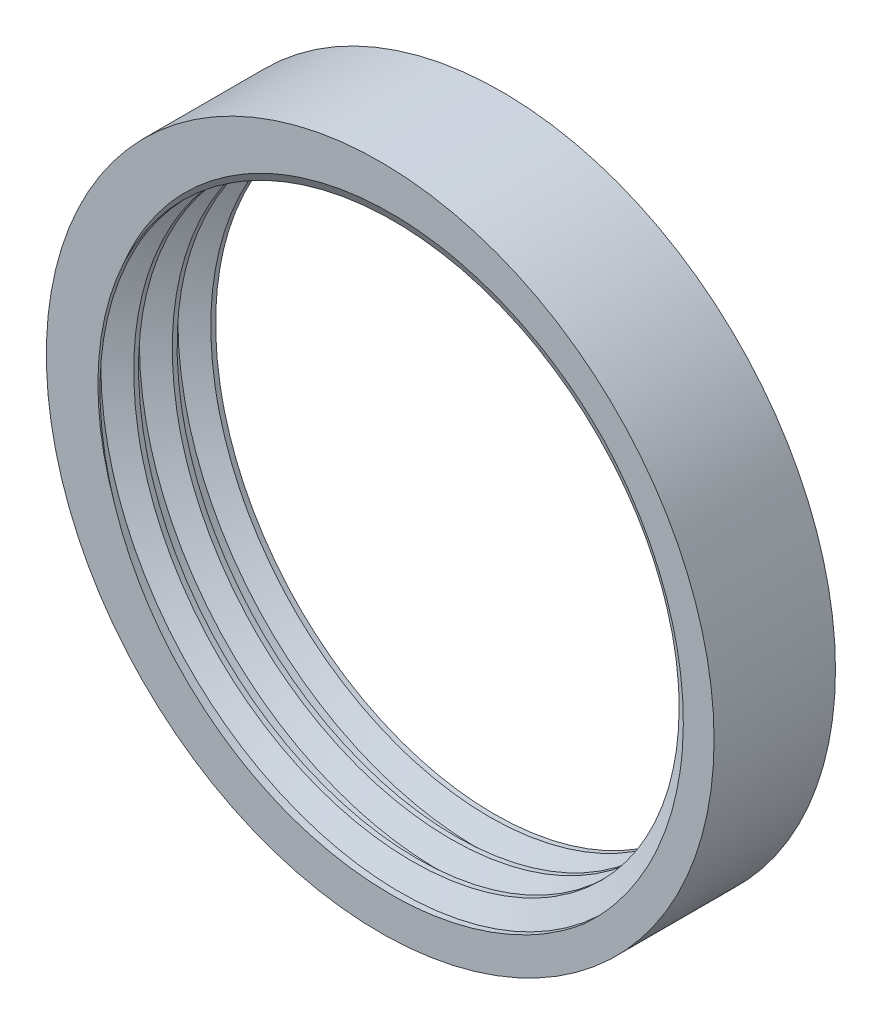
SolidWorks part; units mm, degrees
ref_plane "Plano frontal" through (0, 0, 0) normal (0, 0, 1) x (1, 0, 0)
ref_plane "Plano superior" through (0, 0, 0) normal (0, 1, 0) x (1, 0, 0)
ref_plane "Plano direito" through (0, 0, 0) normal (1, 0, 0) x (0, 0, -1)
sketch "Esboço1" plane through (0, 0, 0) normal (0, 0, 1) x (1, 0, 0)
  circle A0 centre (0, 0) radius 27.5
  circle A1 centre (0, 0) radius 23.25
  dimension "D1" = 46.5
  dimension "D2" = 55
extrude "Ressalto-extrusão1" add sketch "Esboço1" along normal blind 10
thread "Rosca1" pitch 3.175 method cut profile "Perfil da rosca1" start angle 0, offset 3, length 25, pitch 3.175, diameter 46.5
ref_plane "Plano1" through (-23.25, 0, 13) normal (0, 1, 0) x (1, 0, 0)
sketch "Perfil da rosca1" plane through (-23.25, 0, 13) normal (0, 1, 0) x (1, 0, 0)
  line L0 (0, 0) -> (0, 3.175) construction
  line L11 (0, 0) -> (0, 2.7781)
  line L12 (0, 2.7781) -> (-1.7185, 1.7859)
  line L13 (-1.7185, 1.7859) -> (-1.7185, 0.9922)
  line L15 (-1.7185, 0.9922) -> (0, 0)
  line L17 (-1.7185, 1.3891) -> (0, 1.3891) construction
  point P2 (0, 0)
  dimension "Pitch" = 3.175
  dimension "Profile_Angle" = 60
  dimension "Profile_Land" = 0.7937
  dimension "Profile_Height" = 1.7185
